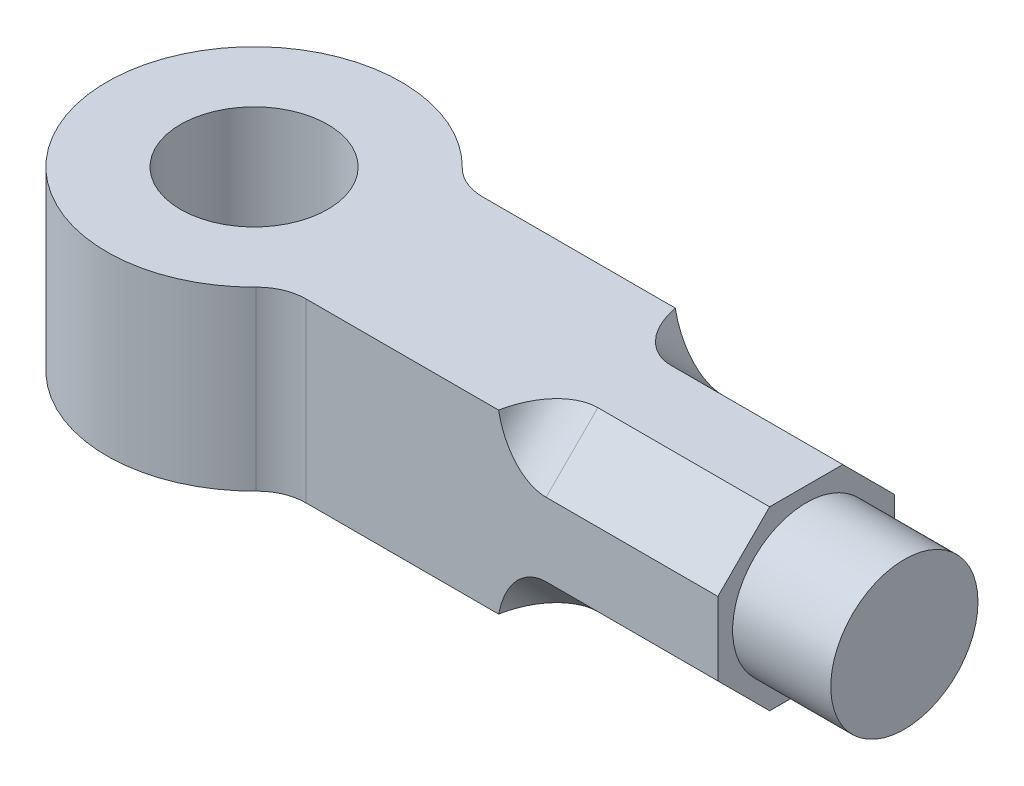
SolidWorks part; units mm, degrees
ref_plane "Front Plane" through (0, 0, 0) normal (0, 0, 1) x (1, 0, 0)
ref_plane "Top Plane" through (0, 0, 0) normal (0, 1, 0) x (1, 0, 0)
ref_plane "Right Plane" through (0, 0, 0) normal (1, 0, 0) x (0, 0, -1)
sketch "Croquis1" plane through (0, 0, 0) normal (0, 1, 0) x (1, 0, 0)
  line L0 (0, 0) -> (22.5, 0) construction
  line L1 (45, 0) -> (120, 0) construction
  line L2 (24, 18) -> (67.5, 18)
  line L4 (24, -18) -> (67.5, -18)
  line L5 (67.5, 18) -> (67.5, -18)
  line L7 (45, 0) -> (67.5, 18) construction
  line L8 (45, 0) -> (67.5, -18) construction
  arc A0 (24, 18) -> (24, -18) centre (0, 0) ccw
  circle A1 centre (0, 0) radius 15
  point P4 (45, 0)
  point P10 (45, 0)
  dimension "D1" = 30
  dimension "D2" = 60
  dimension "D3" = 120
  dimension "D4" = 36
  dimension "D5" = 75
extrude "Saliente-Extruir1" add sketch "Croquis1" along normal mid plane 36
sketch "Croquis2" plane through (67.5, 0, 0) normal (1, 0, 0) x (0, 0, -1)
  line L0 (-18, 18) -> (18, 18) construction
  line L12 (-18, 7.4558) -> (-18, -7.4558)
  line L13 (-18, -7.4558) -> (-7.4558, -18)
  line L14 (-7.4558, -18) -> (7.4558, -18)
  line L15 (7.4558, -18) -> (18, -7.4558)
  line L16 (18, -7.4558) -> (18, 7.4558)
  line L17 (18, 7.4558) -> (7.4558, 18)
  line L18 (7.4558, 18) -> (-7.4558, 18)
  line L19 (-7.4558, 18) -> (-18, 7.4558)
  circle A0 centre (0, 0) radius 18 construction
  dimension "D1" = 36
extrude "Saliente-Extruir2" add sketch "Croquis2" along normal blind 45
sketch "Croquis3" plane through (112.5, 0, 0) normal (1, 0, 0) x (0, 0, -1)
  circle A0 centre (0, 0) radius 15
  dimension "D1" = 30
extrude "Saliente-Extruir3" add sketch "Croquis3" along normal blind 20
fillet "Redondeo1" radius 10 4 edges at (67.5, -12.7279, 12.7279) (67.5, -12.7279, -12.7279) (67.5, 12.7279, -12.7279) (67.5, 12.7279, 12.7279)
fillet "Redondeo2" radius 10 2 edges at (24, 0, -18) (24, 0, 18)
